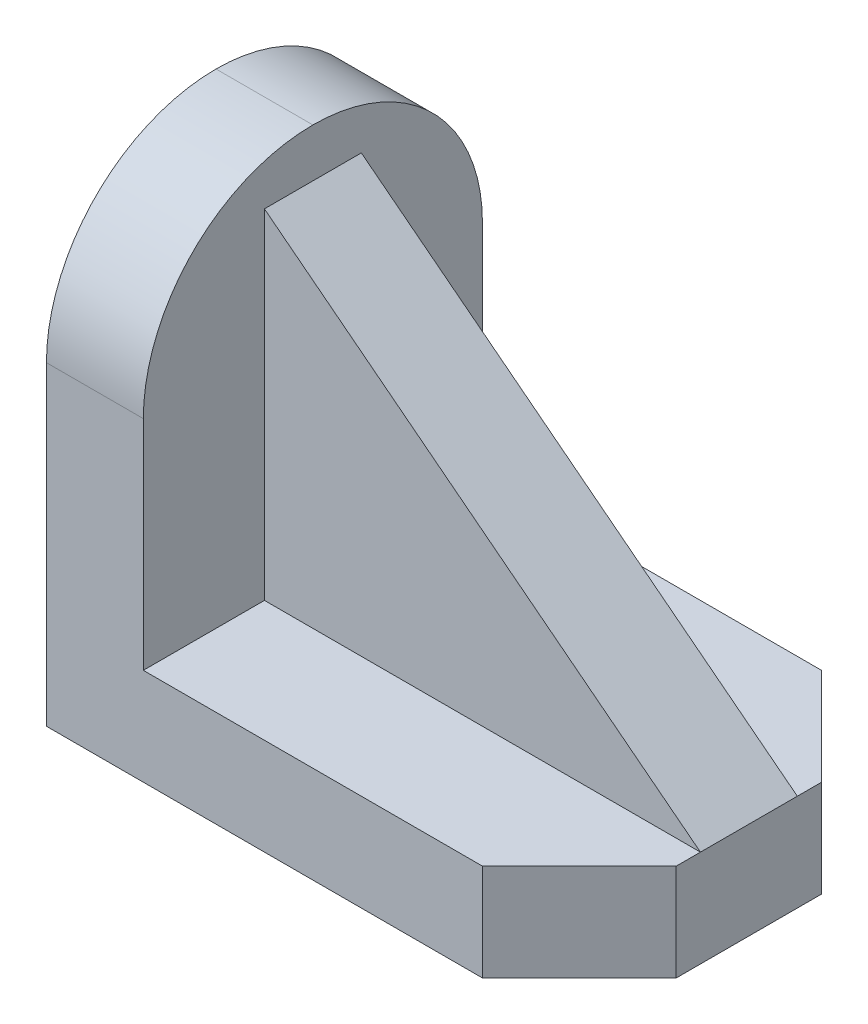
SolidWorks part; units mm, degrees
ref_plane "Front Plane" through (0, 0, 0) normal (0, 0, 1) x (1, 0, 0)
ref_plane "Top Plane" through (0, 0, 0) normal (0, 1, 0) x (1, 0, 0)
ref_plane "Right Plane" through (0, 0, 0) normal (1, 0, 0) x (0, 0, -1)
sketch "Sketch3" plane through (0, 0, 0) normal (0, 1, 0) x (1, 0, 0)
  line L1 (-33, 21) -> (33, 21)
  line L2 (-33, 21) -> (-33, -21)
  line L3 (-33, -21) -> (33, -21)
  line L4 (33, 21) -> (33, -21)
  line L5 (-33, 21) -> (33, -21) construction
  line L6 (-33, -21) -> (33, 21) construction
  point P0 (0, 0)
  dimension "D1" = 42
  dimension "D2" = 66
extrude "Boss-Extrude1" add sketch "Sketch3" along normal blind 12
chamfer "Chamfer1" distance 12 2 edges at (33, 6, -21) (33, 6, 21)
sketch "Sketch4" plane through (0, 12, 0) normal (0, 1, 0) x (1, 0, 0)
  line L0 (-33, -21) -> (21, -21) construction
  line L1 (-33, 21) -> (-21, 21)
  line L2 (-33, 21) -> (-33, -21)
  line L3 (-33, -21) -> (-21, -21)
  line L4 (-21, 21) -> (-21, -21)
  dimension "D1" = 12
extrude "Boss-Extrude2" add sketch "Sketch4" along normal blind 48
fillet "Fillet1" radius 21 2 edges at (-27, 60, 21) (-27, 60, -21)
sketch "Sketch6" plane through (0, 0, 0) normal (0, 0, 1) x (1, 0, 0)
  line L0 (-21, 54) -> (33, 12)
  line L1 (33, 12) -> (-21, 12)
  line L2 (-21, 12) -> (-21, 54)
  dimension "D1" = 42
extrude "Boss-Extrude5" add sketch "Sketch6" along normal mid plane 12
